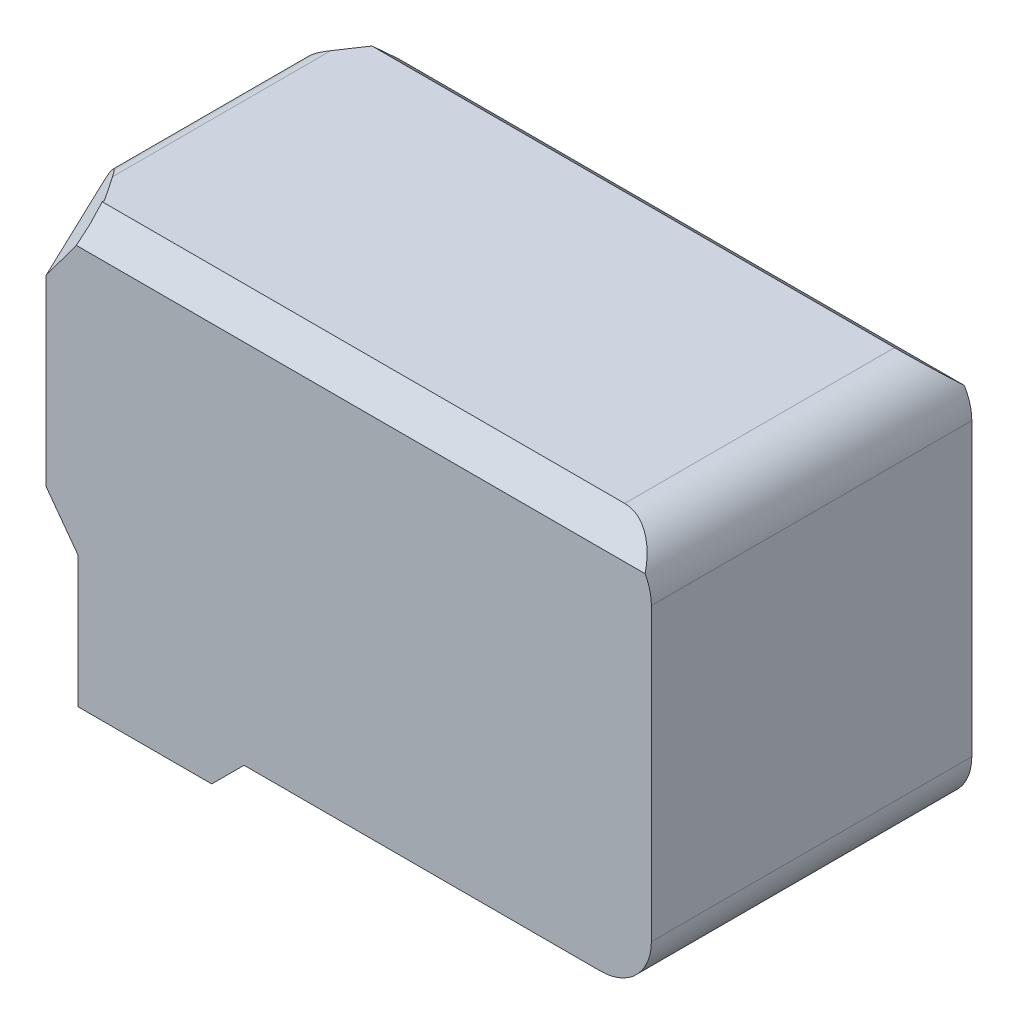
SolidWorks part; units mm, degrees
material "PLA"
ref_plane "Front Plane" through (0, 0, 0) normal (0, 0, 1) x (1, 0, 0)
ref_plane "Top Plane" through (0, 0, 0) normal (0, 1, 0) x (1, 0, 0)
ref_plane "Right Plane" through (0, 0, 0) normal (1, 0, 0) x (0, 0, -1)
sketch "Sketch2" plane through (0, 0, 0) normal (1, 0, 0) x (0, 0, -1)
  line L0 (0, 0) -> (0, 15.615) construction
  line L1 (0, 0) -> (0, -15.615) construction
  line L2 (-15.735, 0) -> (15.735, 0) construction
  line L3 (0, 15.615) -> (-8.5, 15.615)
  line L4 (0, 15.615) -> (8.5, 15.615)
  line L12 (0, -15.615) -> (-8.5, -15.615)
  line L13 (0, -15.615) -> (8.5, -15.615)
  line L18 (-15.735, 0) -> (-15.735, 9)
  line L19 (-15.735, 0) -> (-15.735, -9)
  line L20 (-15.735, -9) -> (-8.5, -15.615)
  line L21 (-15.735, 9) -> (-8.5, 15.615)
  line L22 (15.735, 0) -> (15.735, 9)
  line L23 (15.735, 9) -> (8.5, 15.615)
  line L24 (15.735, 0) -> (15.735, -9)
  line L25 (15.735, -9) -> (8.5, -15.615)
  circle A1 centre (0, 0) radius 7 construction
  circle A2 centre (0, 7) radius 1.375
  circle A3 centre (-7, 0) radius 1.375
  circle A4 centre (7, 0) radius 1.375
  circle A5 centre (0, -7) radius 1.375
  point P17 (0, 0)
  dimension "D1" = 8.5
  dimension "D2" = 14
  dimension "D3" = 2.75
  dimension "D4" = 15.615
  dimension "D5" = 15.615
  dimension "D6" = 31.47
  dimension "D7" = 8.5
  dimension "D8" = 8.5
  dimension "D9" = 8.5
  dimension "D10" = 9
  dimension "D11" = 9
extrude "Boss-Extrude1" add sketch "Sketch2" along normal blind 3.125
sketch "Sketch3" plane through (3.125, 0, 0) normal (-1, 0, 0) x (0, 0, 1)
  line L0 (0, 0) -> (0, -26.145) construction
  line L1 (0, 0) -> (0, 15.615) construction
  line L2 (-15.735, -9) -> (-15.735, -26.145)
  line L3 (-15.735, -26.145) -> (15.735, -26.145)
  line L4 (15.735, -26.145) -> (15.735, -9)
  line L5 (8.5, 15.615) -> (15.735, 15.615)
  line L6 (15.735, 15.615) -> (15.735, 9)
  line L7 (-8.5, 15.615) -> (-15.735, 15.615)
  line L8 (15.735, 9) -> (8.5, 15.615)
  line L9 (8.5, 15.615) -> (-8.5, 15.615)
  line L11 (-8.5, 15.615) -> (-15.735, 9)
  line L15 (8.5, 15.615) -> (-8.5, 15.615)
  line L20 (-15.735, 15.615) -> (-15.735, 9)
  line L24 (-8.5, -15.615) -> (8.5, -15.615)
  line L31 (-15.735, 9) -> (-15.735, -9)
  line L32 (-15.735, 9) -> (-15.735, -9)
  line L33 (-15.735, -9) -> (-8.5, -15.615)
  line L35 (8.5, -15.615) -> (15.735, -9)
  line L37 (15.735, -9) -> (15.735, 9)
  line L38 (15.735, -9) -> (15.735, 9)
  circle A0 centre (0, 0) radius 11
  dimension "D1" = 22
  dimension "D2" = 26.145
  dimension "D3" = 15.615
  dimension "D4" = 0
extrude "Boss-Extrude2" add sketch "Sketch3" against normal blind 4
fillet "Fillet1" radius 3.125 5 edges at (3.125, 12.3075, 12.1175) (3.125, 12.3075, -12.1175) (3.125, -12.3075, -12.1175) (3.125, -15.615, 0) (3.125, -12.3075, 12.1175)
sketch "Sketch4" plane through (7.125, 0, 0) normal (1, 0, 0) x (0, 0, -1)
  line L8 (12.56, 12.44) -> (-12.56, 12.44)
  line L9 (-12.56, 12.44) -> (-12.56, -22.97)
  line L10 (-12.56, -22.97) -> (12.56, -22.97)
  line L11 (12.56, -22.97) -> (12.56, 12.44)
  line L12 (12.56, 12.44) -> (-12.56, 12.44)
  line L13 (-12.56, 12.44) -> (-12.56, -22.97)
  line L14 (-12.56, -22.97) -> (12.56, -22.97)
  line L15 (12.56, -22.97) -> (12.56, 12.44)
  line L16 (15.735, 15.615) -> (-15.735, 15.615)
  line L17 (-15.735, 15.615) -> (-15.735, -26.145)
  line L18 (-15.735, -26.145) -> (15.735, -26.145)
  line L19 (15.735, -26.145) -> (15.735, 15.615)
  line L20 (15.735, 15.615) -> (-15.735, 15.615)
  line L21 (-15.735, 15.615) -> (-15.735, -26.145)
  line L22 (-15.735, -26.145) -> (15.735, -26.145)
  line L23 (15.735, -26.145) -> (15.735, 15.615)
  dimension "D1" = 3.175
  dimension "D2" = 0
extrude "Boss-Extrude3" add sketch "Sketch4" along normal blind 49.135
chamfer "Chamfer1" distance 2.38 angle 47.5 2 edges at (29.6925, 15.615, 15.735) (29.6925, 15.615, -15.735)
sketch "Sketch5" plane through (56.26, 0, 0) normal (1, 0, 0) x (0, 0, -1)
  line L6 (13.1377, 15.615) -> (-13.355, 15.615)
  line L7 (-13.355, 15.615) -> (-15.735, 13.0177)
  line L8 (-15.735, 13.0177) -> (-15.735, -26.145)
  line L9 (-15.735, -26.145) -> (15.735, -26.145)
  line L10 (15.735, -26.145) -> (15.735, 13.235)
  line L11 (15.735, 13.235) -> (13.1377, 15.615)
  line L12 (13.1377, 15.615) -> (-13.355, 15.615)
  line L13 (-13.355, 15.615) -> (-15.735, 13.0177)
  line L14 (-15.735, 13.0177) -> (-15.735, -26.145)
  line L15 (-15.735, -26.145) -> (15.735, -26.145)
  line L16 (15.735, -26.145) -> (15.735, 13.235)
  line L17 (15.735, 13.235) -> (13.1377, 15.615)
  dimension "D1" = 0
extrude "Boss-Extrude4" add sketch "Sketch5" along normal blind 3.175
sketch "Sketch6" plane through (0, -26.145, 0) normal (0, -1, 0) x (1, 0, 0)
  line L0 (59.435, -15.735) -> (3.125, -15.735) construction
  line L1 (59.435, 15.735) -> (19.435, 15.735)
  line L2 (59.435, 15.735) -> (59.435, -15.735)
  line L3 (59.435, -15.735) -> (19.435, -15.735)
  line L4 (19.435, 15.735) -> (19.435, -15.735)
  dimension "D1" = 40
extrude "Cut-Extrude1" cut sketch "Sketch6" against normal blind 3.175
chamfer "Chamfer2" distance 3.175 angle 45 1 edges at (19.435, -26.145, 0)
fillet "Fillet3" radius 5 1 edges at (59.435, 15.615, 0.1087)
fillet "Fillet4" radius 5 1 edges at (59.435, -22.97, 0)
fillet "Fillet5" radius 1.5 1 edges at (0, 15.615, 0)
ref_plane "Plane1" through (29.7175, 0, 0) normal (-1, 0, 0) x (0, 0, 1)
sketch "Sketch7" plane through (29.7175, 0, 0) normal (-1, 0, 0) x (0, 0, 1)
  line L0 (0, 15.615) -> (0, -26.145) construction
  line L1 (-10.723, 15.615) -> (10.723, 15.615) construction
  line L2 (-15.735, -26.145) -> (15.735, -26.145) construction
  line L3 (0, -5.265) -> (15.735, -5.265) construction
  line L4 (15.735, 9) -> (15.735, -9) construction
  line L5 (0, -5.265) -> (-15.735, -5.265) construction
  line L6 (-15.735, -9) -> (-15.735, 9) construction
ref_plane "Plane2" through (0, 0, 0) normal (0, 0, -1) x (-1, 0, 0)
sketch "Sketch8" plane through (0, 0, 0) normal (0, 0, -1) x (-1, 0, 0)
  line L3 (-29.7175, -5.2527) -> (0, -5.2527) construction
  line L4 (0, -9) -> (0, 9) construction
  line L5 (-29.7175, -5.2527) -> (-59.435, -5.2527) construction
  line L6 (-59.435, -17.97) -> (-59.435, 10.615) construction
